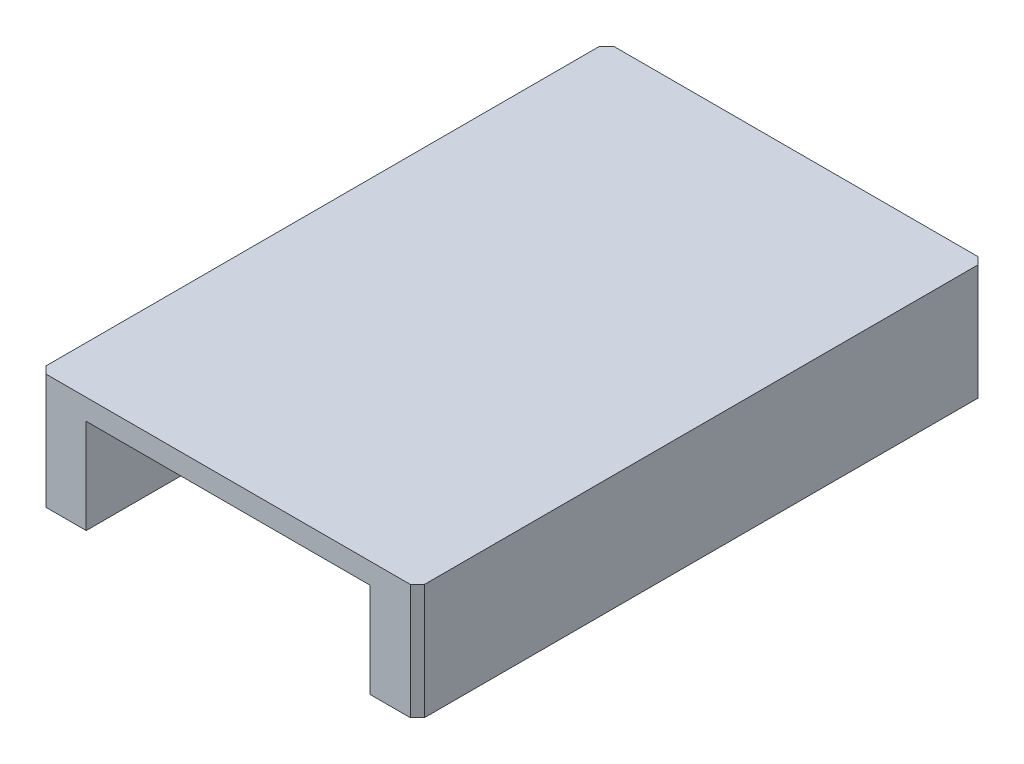
SolidWorks part; units mm, degrees
material "PLA"
ref_plane "Piano frontale" through (0, 0, 0) normal (0, 0, 1) x (1, 0, 0)
ref_plane "Piano superiore" through (0, 0, 0) normal (0, 1, 0) x (1, 0, 0)
ref_plane "Piano destro" through (0, 0, 0) normal (1, 0, 0) x (0, 0, -1)
sketch "Schizzo1" plane through (0, 0, 0) normal (1, 0, 0) x (0, 0, -1)
  line L0 (0, 0) -> (0, 7.2)
  line L1 (0, 7.2) -> (60, 7.2)
  line L2 (60, 7.2) -> (60, 0)
  line L3 (60, 0) -> (0, 0)
  line L8 (33.625, 6.1) -> (33.625, 1.1)
  line L9 (33.625, 1.1) -> (52.75, 1.1)
  line L10 (52.75, 1.1) -> (52.75, 6.1)
  line L11 (52.75, 6.1) -> (33.625, 6.1)
  line L12 (30, 7.2) -> (30, 0) construction
  line L13 (7.25, 1.1) -> (7.25, 6.1)
  line L14 (26.375, 1.1) -> (7.25, 1.1)
  line L15 (26.375, 6.1) -> (26.375, 1.1)
  line L16 (7.25, 6.1) -> (26.375, 6.1)
  dimension "D1" = 7.2
  dimension "D2" = 7.25
  dimension "D3" = 5
  dimension "D4" = 7.25
  dimension "D5" = 60
  dimension "D6" = 1.1
extrude "Estrusione-Estrusione1" add sketch "Schizzo1" along normal blind 40
sketch "Schizzo2" plane through (0, 0, 0) normal (0, 0, 1) x (1, 0, 0)
  line L0 (5, 0) -> (5, 5)
  line L1 (40, 0) -> (0, 0) construction
  line L2 (5, 5) -> (16.375, 5)
  line L3 (16.375, 5) -> (16.375, 0)
  line L4 (16.375, 0) -> (5, 0)
  line L5 (20, 7.2) -> (20, 0) construction
  line L6 (40, 7.2) -> (0, 7.2) construction
  line L8 (0, 7.2) -> (0, 0) construction
  line L9 (23.625, 5) -> (23.625, 0)
  line L14 (14.3, 7.2) -> (16.375, 7.2)
  line L15 (14.3, 7.2) -> (14.3, 6.1)
  line L16 (14.3, 6.1) -> (16.375, 6.1)
  line L17 (16.375, 7.2) -> (16.375, 6.1)
  line L18 (7.25, 7.2) -> (9.3, 7.2)
  line L19 (7.25, 7.2) -> (7.25, 6.1)
  line L20 (7.25, 6.1) -> (9.3, 6.1)
  line L21 (9.3, 7.2) -> (9.3, 6.1)
  line L22 (35, 5) -> (23.625, 5)
  line L23 (35, 0) -> (35, 5)
  line L24 (23.625, 0) -> (35, 0)
  line L25 (25.7, 6.1) -> (23.625, 6.1)
  line L26 (23.625, 7.2) -> (23.625, 6.1)
  line L27 (25.7, 7.2) -> (23.625, 7.2)
  line L28 (25.7, 7.2) -> (25.7, 6.1)
  line L29 (32.75, 6.1) -> (30.7, 6.1)
  line L30 (30.7, 7.2) -> (30.7, 6.1)
  line L31 (32.75, 7.2) -> (30.7, 7.2)
  line L32 (32.75, 7.2) -> (32.75, 6.1)
  dimension "D1" = 5
  dimension "D2" = 3.625
  dimension "D3" = 2.2
  dimension "D4" = 1.1
  dimension "D5" = 7.25
  dimension "D6" = 3.625
  dimension "D7" = 21.4
  dimension "D8" = 1.1
  dimension "D9" = 5
extrude "Taglio-Estrusione1" cut sketch "Schizzo2" against normal through all
chamfer "Smusso1" distance 0.75 angle 45 4 edges at (0, 3.6, -60) (40, 3.6, -60) (40, 3.6, 0) (0, 3.6, 0)
sketch "Schizzo3" plane through (0, 0, 0) normal (0, 0, 1) x (1, 0, 0)
  line L1 (16.375, 0) -> (23.625, 0)
  line L2 (16.375, 0) -> (16.375, 5)
  line L3 (16.375, 5) -> (23.625, 5)
  line L4 (23.625, 0) -> (23.625, 5)
extrude "Taglio-Estrusione2" cut sketch "Schizzo3" against normal blind 64
sketch "Schizzo4" plane through (0, 0, 0) normal (0, 0, 1) x (1, 0, 0)
  line L6 (39.25, 0) -> (39.25, 7.2) construction
  line L7 (0.75, 7.2) -> (39.25, 7.2)
  line L8 (0.75, 7.2) -> (0.75, 6.1)
  line L9 (0.75, 6.1) -> (39.25, 6.1)
  line L10 (39.25, 7.2) -> (39.25, 6.1)
  dimension "D1" = 1.1
extrude "Estrusione-Estrusione3" add sketch "Schizzo4" against normal blind 60
sketch "Schizzo7" plane through (0, 0, -52.75) normal (0, 0, 1) x (1, 0, 0)
  line L0 (40, 6.1) -> (0, 6.1) construction
  line L1 (35, 5) -> (5, 5)
  line L2 (35, 5) -> (35, 6.1)
  line L3 (35, 6.1) -> (5, 6.1)
  line L4 (5, 5) -> (5, 6.1)
  point P7 (0, 0)
extrude "Estrusione-Estrusione4" add sketch "Schizzo7" along normal blind 50
sketch "Schizzo8" plane through (0, 0, 0) normal (0, -1, 0) x (1, 0, 0)
  line L0 (5, 0) -> (0.75, 0)
  line L1 (0.75, 0) -> (0, -0.75)
  line L2 (0, -0.75) -> (0, -59.25)
  line L3 (0, -59.25) -> (0.75, -60)
  line L4 (0.75, -60) -> (5, -60)
  line L5 (5, -60) -> (5, 0)
  line L6 (35, 0) -> (35, -60)
  line L7 (35, -60) -> (39.25, -60)
  line L8 (39.25, -60) -> (40, -59.25)
  line L9 (40, -59.25) -> (40, -0.75)
  line L10 (40, -0.75) -> (39.25, 0)
  line L11 (39.25, 0) -> (35, 0)
extrude "Estrusione-Estrusione5" add sketch "Schizzo8" along normal blind 5
sketch "Schizzo9" plane through (35, 0, 0) normal (1, 0, 0) x (0, 0, -1)
  line L1 (7.25, 6.1) -> (26.375, 6.1)
  line L2 (7.25, 6.1) -> (7.25, 5)
  line L3 (7.25, 5) -> (26.375, 5)
  line L4 (26.375, 6.1) -> (26.375, 5)
  line L5 (33.625, 6.1) -> (52.75, 6.1)
  line L6 (33.625, 6.1) -> (33.625, 5)
  line L7 (33.625, 5) -> (52.75, 5)
  line L8 (52.75, 6.1) -> (52.75, 5)
extrude "Estrusione-Estrusione6" add sketch "Schizzo9" along normal blind 5 and the other way blind 35
sketch "Schizzo10" plane through (0, 0, 0) normal (-1, 0, 0) x (0, 0, 1)
  line L1 (-52.75, 1.1) -> (-33.625, 1.1)
  line L2 (-52.75, 1.1) -> (-52.75, -2.8)
  line L3 (-52.75, -2.8) -> (-33.625, -2.8)
  line L4 (-33.625, 1.1) -> (-33.625, -2.8)
  line L5 (-26.375, 1.1) -> (-7.25, 1.1)
  line L6 (-26.375, 1.1) -> (-26.375, -2.8)
  line L7 (-26.375, -2.8) -> (-7.25, -2.8)
  line L8 (-7.25, 1.1) -> (-7.25, -2.8)
  line L10 (-33.625, 5) -> (-52.75, 5) construction
  line L11 (-7.25, 5) -> (-26.375, 5) construction
  dimension "D1" = 3.9
extrude "Taglio-Estrusione3" cut sketch "Schizzo10" against normal through all
sketch "Schizzo12" plane through (40, 0, 0) normal (1, 0, 0) x (0, 0, -1)
  line L1 (7.25, 5) -> (26.375, 5)
  line L2 (7.25, 5) -> (7.25, -2.8)
  line L3 (7.25, -2.8) -> (26.375, -2.8)
  line L4 (26.375, 5) -> (26.375, -2.8)
  line L5 (33.625, 5) -> (52.75, 5)
  line L6 (33.625, 5) -> (33.625, -2.8)
  line L7 (33.625, -2.8) -> (52.75, -2.8)
  line L8 (52.75, 5) -> (52.75, -2.8)
extrude "Estrusione-Estrusione7" add sketch "Schizzo12" against normal blind 40
sketch "Schizzo13" plane through (0, 0, -7.25) normal (0, 0, 1) x (1, 0, 0)
  line L0 (5, -5) -> (5, 5)
  line L1 (5, 5) -> (35, 5)
  line L2 (35, 5) -> (35, -5)
  line L3 (35, -5) -> (5, -5)
extrude "Taglio-Estrusione4" cut sketch "Schizzo13" against normal blind 66
